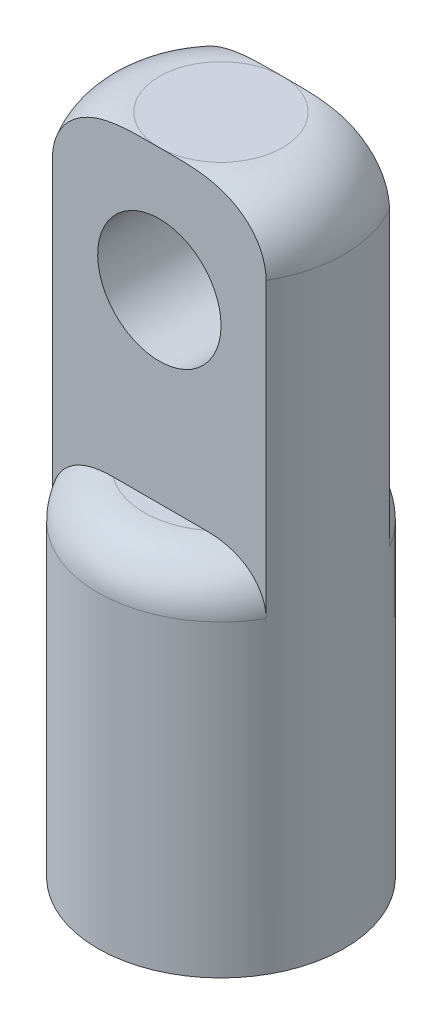
SolidWorks part; units mm, degrees
ref_plane "前视基准面" through (0, 0, 0) normal (0, 0, 1) x (1, 0, 0)
ref_plane "上视基准面" through (0, 0, 0) normal (0, 1, 0) x (1, 0, 0)
ref_plane "右视基准面" through (0, 0, 0) normal (1, 0, 0) x (0, 0, -1)
sketch "草图1" plane through (0, 0, 0) normal (0, 1, 0) x (1, 0, 0)
  circle A0 centre (0, 0) radius 8
  dimension "D1" = 16
extrude "凸台-拉伸1" add sketch "草图1" along normal blind 43
sketch "草图2" plane through (0, 0, 0) normal (1, 0, 0) x (0, 0, -1)
  line L0 (0, 0) -> (0, 44674.3389) construction
  line L1 (-8, 43) -> (-4, 43)
  line L2 (-8, 43) -> (-8, 23)
  line L3 (-8, 23) -> (-4, 23)
  line L4 (-4, 43) -> (-4, 23)
  line L5 (8, 43) -> (4, 43)
  line L6 (8, 43) -> (8, 23)
  line L7 (8, 23) -> (4, 23)
  line L8 (4, 43) -> (4, 23)
  point P13 (0, 0)
  point P14 (0, 0)
  point P15 (0, 0)
  dimension "D1" = 8
  dimension "D2" = 20
extrude "切除-拉伸1" cut sketch "草图2" against normal mid plane 43
fillet "圆角1" radius 3 2 edges at (0, 23, 8) (0, 23, -8)
fillet "圆角2" radius 4 2 edges at (8, 43, 0) (-8, 43, 0)
sketch "草图3" plane through (0, 0, 4) normal (0, 0, 1) x (1, 0, 0)
  circle A0 centre (0, 35) radius 4
  point P4 (0, 0)
  dimension "D1" = 8
  dimension "D2" = 35
extrude "切除-拉伸2" cut sketch "草图3" against normal mid plane 43
sketch "草图4" plane through (0, 0, 0) normal (0, -1, 0) x (1, 0, 0)
  circle A0 centre (0, 0) radius 4
  dimension "D1" = 8
extrude "切除-拉伸3" cut sketch "草图4" against normal blind 20
